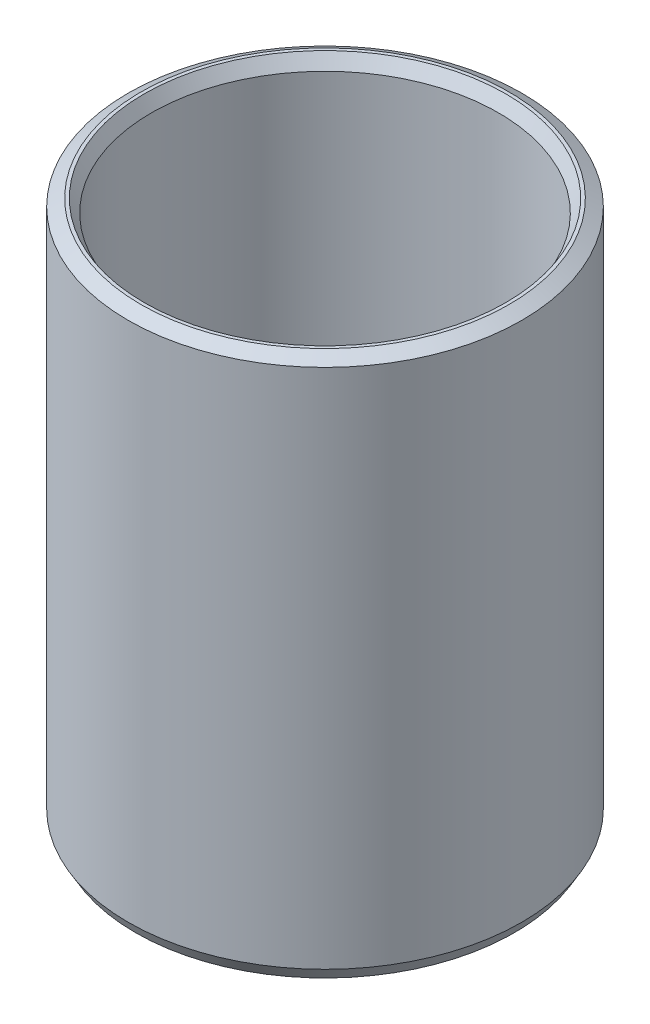
SolidWorks part; units mm, degrees
ref_plane "Front Plane" through (0, 0, 0) normal (0, 0, 1) x (1, 0, 0)
ref_plane "Top Plane" through (0, 0, 0) normal (0, 1, 0) x (1, 0, 0)
ref_plane "Right Plane" through (0, 0, 0) normal (1, 0, 0) x (0, 0, -1)
sketch "Sketch1" plane through (0, 0, 0) normal (0, 1, 0) x (1, 0, 0)
  circle A0 centre (0, 0) radius 60
  dimension "SLEEVE_OD" = 120
extrude "Boss-Extrude1" add sketch "Sketch1" along normal blind 165.0183
sketch "Sketch2" plane through (0, 0, 0) normal (0, 1, 0) x (1, 0, 0)
  circle A0 centre (0, 0) radius 52.8868
  dimension "BORE_D" = 105.7735
extrude "Cut-Extrude1" cut sketch "Sketch2" along normal through all
chamfer "Chamfer1" distance 2.2378 angle 60 4 edges at (0, 165.0183, 52.8868) (0, 0, 52.8868) (0, 0, 60) (0, 165.0183, 60) first distance on face at (0, 165.0183, 52.8868) first distance on face at (0, 0, 52.8868) first distance on face at (0, 165.0183, 60)
